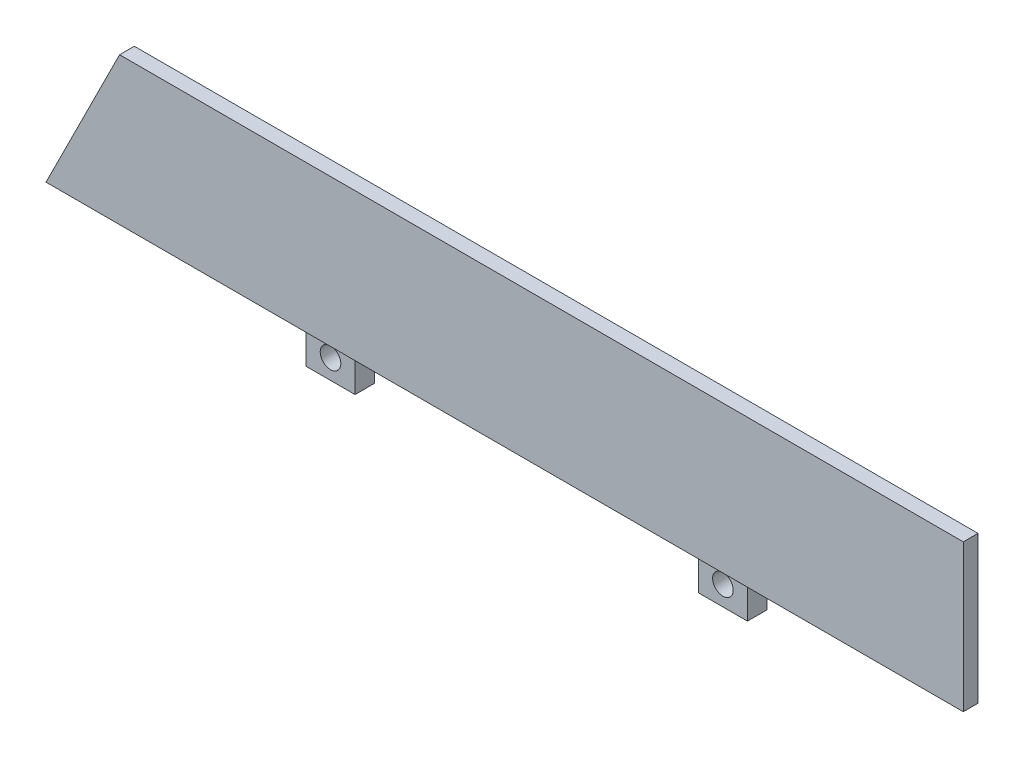
SolidWorks part; units mm, degrees
material "ABS"
ref_plane "Płaszczyzna przednia" through (0, 0, 0) normal (0, 0, 1) x (1, 0, 0)
ref_plane "Płaszczyzna górna" through (0, 0, 0) normal (0, 1, 0) x (1, 0, 0)
ref_plane "Płaszczyzna prawa" through (0, 0, 0) normal (1, 0, 0) x (0, 0, -1)
sketch "Szkic1" plane through (0, 0, 0) normal (0, 0, 1) x (1, 0, 0)
  line L0 (0, 0) -> (187, 0)
  line L1 (187, 0) -> (187, 30)
  line L2 (187, 30) -> (15, 30)
  line L3 (15, 30) -> (0, 0)
  dimension "D1" = 187
  dimension "D2" = 30
  dimension "D3" = 172
extrude "Dodanie-wyciągnięcie1" add sketch "Szkic1" along normal blind 3
sketch "Szkic2" plane through (0, 0, 0) normal (0, 0, -1) x (-1, 0, 0)
  line L1 (0, 0) -> (-187, 0) construction
  line L2 (-140, 5) -> (-130, 5)
  line L3 (-60, 5) -> (-50, 5)
  line L4 (-60, 5) -> (-60, -9)
  line L5 (-60, -9) -> (-50, -9)
  line L6 (-50, 5) -> (-50, -9)
  line L7 (-140, 5) -> (-140, -9)
  line L8 (-140, -9) -> (-130, -9)
  line L9 (-130, 5) -> (-130, -9)
  circle A0 centre (-55, -5) radius 2.1
  circle A1 centre (-135, -5) radius 2.1
  point P11 (-55, -9)
  dimension "D5" = 4.2
  dimension "D1" = 55
  dimension "D2" = 4
  dimension "D3" = 10
  dimension "D4" = 9
  dimension "D6" = 14
  dimension "D7" = 2
extrude "Dodanie-wyciągnięcie2" add sketch "Szkic2" along normal blind 4
chamfer "Sfazowanie1" distance 4 angle 45 6 edges at (60, 2.5, 0) (55, 5, 0) (50, 2.5, 0) (140, 2.5, 0) (135, 5, 0) (130, 2.5, 0)
